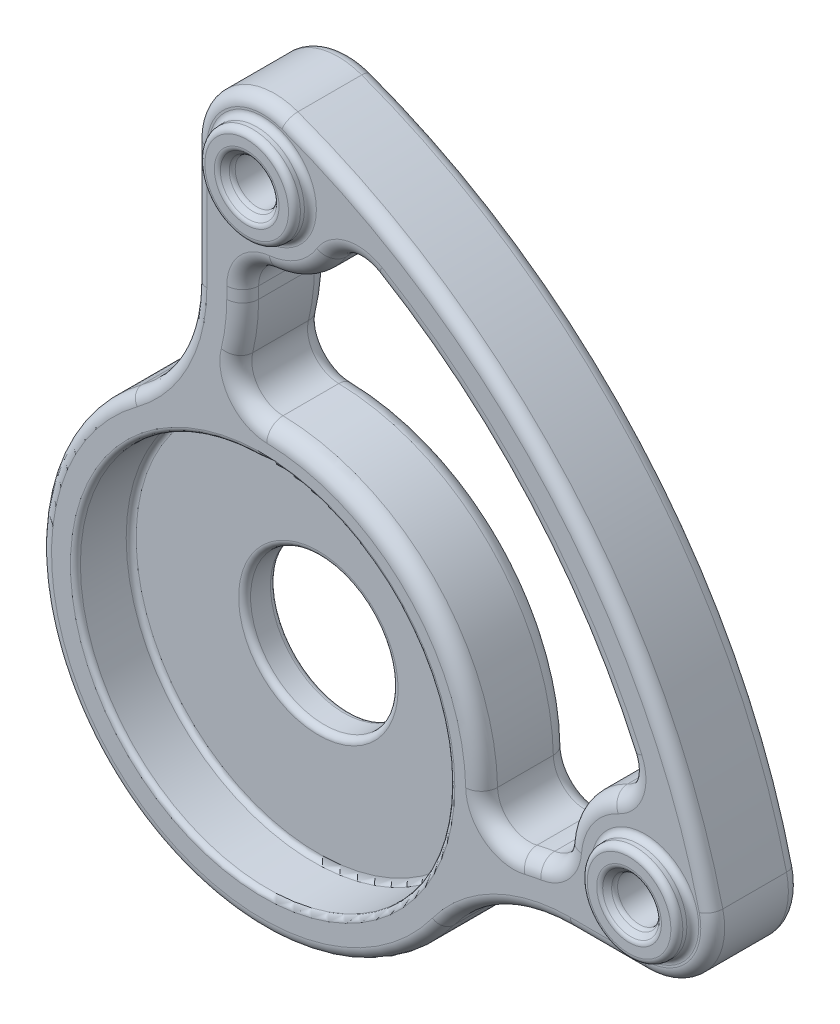
SolidWorks part; units mm, degrees
ref_plane "Front Plane" through (0, 0, 0) normal (0, 0, 1) x (1, 0, 0)
ref_plane "Top Plane" through (0, 0, 0) normal (0, 1, 0) x (1, 0, 0)
ref_plane "Right Plane" through (0, 0, 0) normal (1, 0, 0) x (0, 0, -1)
sketch "Sketch1" plane through (0, 0, 0) normal (0, 0, 1) x (1, 0, 0)
  line L0 (-4.25, 27) -> (-4.25, 19.3116)
  line L1 (24, -4.25) -> (19.3116, -4.25)
  circle A0 centre (0, 0) radius 4.63
  arc A1 (-8.3125, 11.2651) -> (11.2651, -8.3125) centre (0, 0) ccw
  circle A2 centre (0, 27) radius 1.375
  circle A3 centre (24, 0) radius 1.375
  arc A4 (1.4667, 30.9889) -> (-4.25, 27) centre (0, 27) ccw
  arc A5 (24, -4.25) -> (28.1333, 0.9889) centre (24, 0) ccw
  arc A6 (28.1333, 0.9889) -> (1.4667, 30.9889) centre (-13.2001, -8.9001) ccw
  arc A7 (19.3116, -4.25) -> (11.2651, -8.3125) centre (19.3116, -14.25) ccw
  arc A8 (-4.25, 19.3116) -> (-8.3125, 11.2651) centre (-14.25, 19.3116) cw
  dimension "D1" = 9.26
  dimension "D2" = 28
  dimension "D3" = 2.75
  dimension "D6" = 8.5
  dimension "D7" = 8.5
  dimension "D8" = 85
  dimension "D9" = 10
  dimension "D4" = 27
  dimension "D5" = 24
extrude "Boss-Extrude1" add sketch "Sketch1" along normal blind 5.5
sketch "Sketch2" plane through (0, 0, 5.5) normal (0, 0, 1) x (1, 0, 0)
  circle A0 centre (0, 27) radius 3
  circle A1 centre (24, 0) radius 3
  circle A2 centre (24, 0) radius 1.375 construction
  circle A3 centre (0, 27) radius 1.375 construction
  circle A4 centre (24, 0) radius 1.375
  circle A5 centre (0, 27) radius 1.375
  dimension "D1" = 6
extrude "Boss-Extrude2" add sketch "Sketch2" along normal blind 1
sketch "Sketch3" plane through (0, 0, 5.5) normal (0, 0, 1) x (1, 0, 0)
  line L2 (-1.25, 19.3116) -> (-1.25, 27)
  line L3 (-1.25, 19.3116) -> (-1.25, 22.1588)
  line L4 (24, -1.25) -> (19.3116, -1.25)
  circle A0 centre (0, 0) radius 11.75
  arc A3 (19.3116, -1.25) -> (8.8511, -6.5313) centre (19.3116, -14.25) ccw
  arc A4 (25.2157, 0.2909) -> (0.4314, 28.1732) centre (-13.2001, -8.9001) ccw
  arc A5 (23.7752, 4.9949) -> (4.9341, 26.1912) centre (-13.2001, -8.9001) ccw
  arc A6 (19.159, -1.2509) -> (13.4976, -2.6226) centre (19.3116, -14.25) ccw
  arc A7 (-6.5312, 8.8511) -> (-1.25, 19.3116) centre (-14.25, 19.3116) ccw
  arc A8 (-2.6226, 13.4976) -> (-1.25, 19.3116) centre (-14.25, 19.3116) ccw
  circle A10 centre (24, 0) radius 5
  arc A11 (23.7752, 4.9949) -> (19.159, -1.2509) centre (24, 0) ccw
  circle A13 centre (0, 27) radius 5
  arc A14 (-1.25, 22.1588) -> (4.9341, 26.1912) centre (0, 27) ccw
  arc A15 (13.4976, -2.6226) -> (-2.6226, 13.4976) centre (0, 0) ccw
  circle A18 centre (0, 0) radius 13.75 construction
  circle M16 centre (0, 0) radius 4.63
  dimension "D1" = 23.5
  dimension "D2" = 3
  dimension "D3" = 3
  dimension "D4" = 2
  dimension "D5" = 2
  dimension "D6" = 3
  dimension "D7" = 2
extrude "Cut-Extrude1" cut sketch "Sketch3" against normal blind 3.5 contours A0 M16 region at (6.4231, 9.4396, 5.5)
extrude "Cut-Extrude2" cut sketch "Sketch3<3>" against normal through all contours A15 A11 A5 A14 L3 A8 region at (11.2082, 13.0572, 5.5)
sketch "Sketch3<3>" plane through (0, 0, 5.5) normal (0, 0, 1) x (1, 0, 0) same geometry as "Sketch3"
fillet "Fillet1" radius 2 6 edges at (23.7752, 4.9949, 2.75) (4.9341, 26.1912, 2.75) (-1.25, 22.1588, 2.75) (-2.6226, 13.4976, 2.75) (19.159, -1.2509, 2.75) (13.4976, -2.6226, 2.75)
fillet "Fillet2" radius 1 26 edges at (-0.738, 21.3766, 0) (-1.2655, 14.528, 0) (9.7227, 9.7227, 0) (19.9006, 2.8627, 0) (22.9306, 5.6489, 0) (16.3225, 17.3422, 0) (5.4846, 25.2756, 0) (-0.738, 21.3766, 5.5) (-1.2655, 14.528, 5.5) (9.7227, 9.7227, 5.5) (19.9006, 2.8627, 5.5) (22.9306, 5.6489, 5.5) (16.3225, 17.3422, 5.5) (5.4846, 25.2756, 5.5) (2.6705, 22.7729, 0) (2.6705, 22.7729, 5.5) (-1.3435, 17.7556, 0) (-1.3435, 17.7556, 5.5) (-1.25, 19.6759, 0) (-1.25, 19.6759, 5.5) (14.528, -1.2655, 0) (16.773, -1.5003, 0) (18.4871, -0.7887, 0) (14.528, -1.2655, 5.5) (16.773, -1.5003, 5.5) (18.4871, -0.7887, 5.5)
fillet "Fillet3" radius 0.75 16 edges at (27.3366, -2.6325, 0) (21.6558, -4.25, 0) (14.8047, -5.3232, 0) (-9.8995, -9.8995, 0) (-5.3232, 14.8047, 0) (-4.25, 23.1558, 0) (-2.432, 30.4854, 0) (27.3366, -2.6325, 5.5) (21.6558, -4.25, 5.5) (14.8047, -5.3232, 5.5) (-9.8995, -9.8995, 5.5) (-5.3232, 14.8047, 5.5) (-4.25, 23.1558, 5.5) (-2.432, 30.4854, 5.5) (18.5648, 19.3353, 0) (18.5648, 19.3353, 5.5)
chamfer "Chamfer1" distance 0.5 angle 45 2 edges at (25.375, 0, 6.5) (1.375, 27, 6.5)
fillet "Fillet4" radius 0.375 12 edges at (4.63, 0, 0) (1.375, 27, 0) (25.375, 0, 0) (27, 0, 6.5) (27, 0, 5.5) (3, 27, 5.5) (3, 27, 6.5) (4.63, 0, 2) (25.375, 0, 6) (25.875, 0, 6.5) (1.375, 27, 6) (1.875, 27, 6.5)
fillet "Fillet5" radius 0.3125 2 edges at (11.75, 0, 5.5) (11.75, 0, 2)
